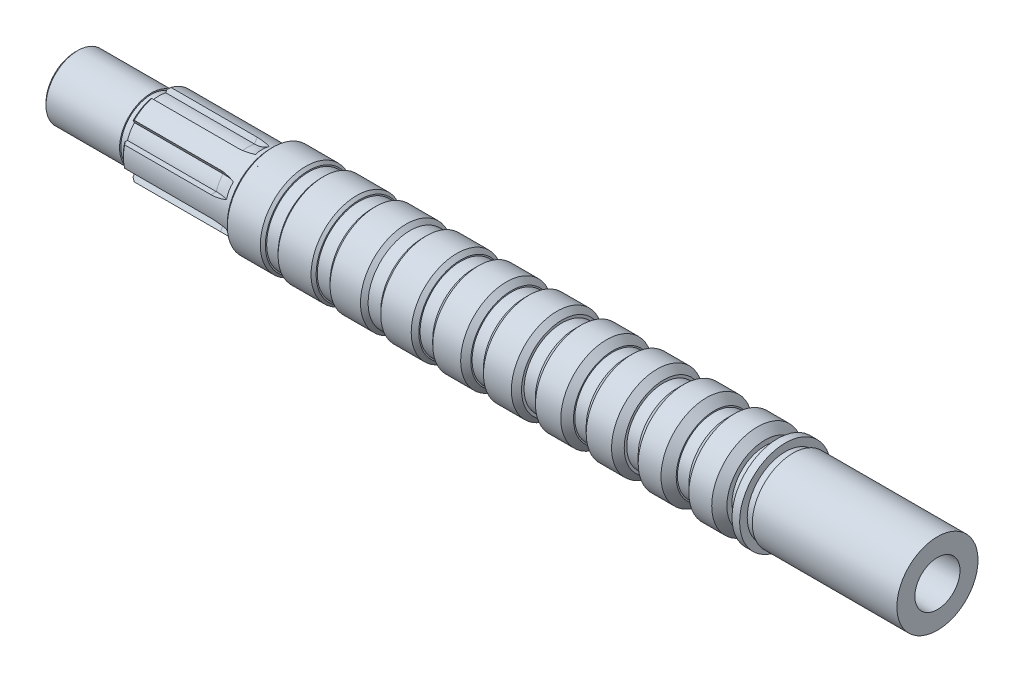
SolidWorks part; units mm, degrees
ref_plane "前视基准面" through (0, 0, 0) normal (0, 0, 1) x (1, 0, 0)
ref_plane "上视基准面" through (0, 0, 0) normal (0, 1, 0) x (1, 0, 0)
ref_plane "右视基准面" through (0, 0, 0) normal (1, 0, 0) x (0, 0, -1)
sketch "草图1" plane through (0, 0, 0) normal (1, 0, 0) x (0, 0, -1)
  circle A0 centre (0, 0) radius 12.5
  dimension "D1" = 25
extrude "凸台-拉伸1" add sketch "草图1" along normal blind 340
sketch "草图3" plane through (340, 0, 0) normal (1, 0, 0) x (0, 0, -1)
  circle A0 centre (0, 0) radius 16
  dimension "D1" = 32
extrude "凸台-拉伸2" add sketch "草图3" against normal blind 60
sketch "草图4" plane through (280, 0, 0) normal (-1, 0, 0) x (0, 0, 1)
  circle A2 centre (0, 0) radius 15
  circle A3 centre (0, 0) radius 15
  dimension "D1" = 1
extrude "切除-拉伸1" cut sketch "草图4" against normal blind 3 flip side to cut
sketch "草图5" plane through (280, 0, 0) normal (-1, 0, 0) x (0, 0, 1)
  circle A0 centre (0, 0) radius 18
  dimension "D1" = 36
extrude "凸台-拉伸3" add sketch "草图5" along normal blind 3
ref_plane "基准面1" through (272, 0, 0) normal (-1, 0, 0) x (0, 0, 1)
sketch "草图6" plane through (272, 0, 0) normal (-1, 0, 0) x (0, 0, 1)
  circle A0 centre (0, 0) radius 18
  dimension "D1" = 36
extrude "凸台-拉伸4" add sketch "草图6" along normal blind 15
pattern_linear "阵列(线性)1" count 10 spacing 20 along (-1, 0, 0) of "凸台-拉伸4"
sketch "草图7" plane through (92, 0, 0) normal (1, 0, 0) x (0, 0, -1)
  circle A2 centre (0, 0) radius 16.5
  circle A3 centre (0, 0) radius 16.5
  dimension "D1" = 1.5
extrude "凸台-拉伸5" add sketch "草图7" along normal up to next
sketch "草图8" plane through (112, 0, 0) normal (1, 0, 0) x (0, 0, -1)
  circle A2 centre (0, 0) radius 16.5
  circle A3 centre (0, 0) radius 16.5
  dimension "D1" = 1.5
extrude "凸台-拉伸6" add sketch "草图8" along normal up to next
sketch "草图9" plane through (132, 0, 0) normal (1, 0, 0) x (0, 0, -1)
  circle A2 centre (0, 0) radius 16.5
  circle A3 centre (0, 0) radius 16.5
  dimension "D1" = 1.5
extrude "凸台-拉伸7" add sketch "草图9" along normal up to next
sketch "草图10" plane through (152, 0, 0) normal (1, 0, 0) x (0, 0, -1)
  circle A2 centre (0, 0) radius 16
  circle A3 centre (0, 0) radius 16
  dimension "D1" = 2
extrude "凸台-拉伸8" add sketch "草图10" along normal up to next
sketch "草图11" plane through (172, 0, 0) normal (1, 0, 0) x (0, 0, -1)
  circle A2 centre (0, 0) radius 15.5
  circle A3 centre (0, 0) radius 15.5
  dimension "D1" = 2.5
extrude "凸台-拉伸9" add sketch "草图11" along normal up to next
sketch "草图12" plane through (192, 0, 0) normal (1, 0, 0) x (0, 0, -1)
  circle A2 centre (0, 0) radius 15
  circle A3 centre (0, 0) radius 15
  dimension "D1" = 3
extrude "凸台-拉伸10" add sketch "草图12" along normal up to next
sketch "草图13" plane through (212, 0, 0) normal (1, 0, 0) x (0, 0, -1)
  circle A2 centre (0, 0) radius 15
  circle A3 centre (0, 0) radius 15
  dimension "D1" = 3
extrude "凸台-拉伸11" add sketch "草图13" along normal up to next
sketch "草图14" plane through (232, 0, 0) normal (1, 0, 0) x (0, 0, -1)
  circle A2 centre (0, 0) radius 14.5
  circle A3 centre (0, 0) radius 14.5
  dimension "D1" = 3.5
extrude "凸台-拉伸12" add sketch "草图14" along normal up to next
sketch "草图15" plane through (252, 0, 0) normal (1, 0, 0) x (0, 0, -1)
  circle A2 centre (0, 0) radius 14.5
  circle A3 centre (0, 0) radius 14.5
  dimension "D1" = 3.5
extrude "凸台-拉伸13" add sketch "草图15" along normal up to next
sketch "草图16" plane through (272, 0, 0) normal (1, 0, 0) x (0, 0, -1)
  circle A2 centre (0, 0) radius 13
  circle A3 centre (0, 0) radius 13
  dimension "D1" = 5
extrude "凸台-拉伸14" add sketch "草图16" along normal up to next
sketch "草图17" plane through (77, 0, 0) normal (-1, 0, 0) x (0, 0, 1)
  circle A0 centre (0, 0) radius 15
  dimension "D1" = 30
extrude "凸台-拉伸15" add sketch "草图17" along normal blind 44
sketch "草图18" plane through (33, 0, 0) normal (-1, 0, 0) x (0, 0, 1)
  circle A0 centre (0, 0) radius 12.5
  circle A1 centre (0, 0) radius 12
  dimension "D1" = 25
  dimension "D2" = 0.5
extrude "切除-拉伸2" cut sketch "草图18" along normal blind 3
chamfer "倒角6" distance 1 angle 45 1 edges at (0, 0, -12.5)
sketch "草图20" plane through (0, 0, 0) normal (0, 0, 1) x (1, 0, 0)
  line L0 (33, 13) -> (68, 13)
  line L1 (33, 15) -> (33, -15) construction
  line L2 (19.8, 0) -> (-19.8, 0) construction
  arc A0 (68, 13) -> (75.9564, 17.7934) centre (68, 22) ccw
  dimension "D1" = 9
  dimension "D2" = 13
  dimension "D3" = 35
sketch "草图21" plane through (33, 0, 0) normal (-1, 0, 0) x (0, 0, 1)
  line L0 (14.4568, 4) -> (12.3693, 4) construction
  line L1 (12.3693, -4) -> (14.4568, -4) construction
  line L5 (2.7206, -12.7121) -> (3.7643, -14.52) construction
  line L6 (10.6925, -10.52) -> (9.6488, -8.7121) construction
  line L7 (-9.6488, -8.7121) -> (-10.6925, -10.52) construction
  line L8 (-3.7643, -14.52) -> (-2.7206, -12.7121) construction
  line L9 (-12.3693, 4) -> (-14.4568, 4) construction
  line L10 (-14.4568, -4) -> (-12.3693, -4) construction
  line L11 (-2.7206, 12.7121) -> (-3.7643, 14.52)
  line L12 (-10.6925, 10.52) -> (-9.6488, 8.7121) construction
  line L13 (9.6488, 8.7121) -> (10.6925, 10.52) construction
  line L14 (3.7643, 14.52) -> (2.7206, 12.7121)
  arc A1 (-3.7643, -14.52) -> (3.7643, -14.52) centre (0, 0) ccw construction
  arc A2 (12.3693, 4) -> (9.6488, 8.7121) centre (0, 0) ccw construction
  circle A3 centre (0, 0) radius 13 construction
  arc A4 (-3.7643, 14.52) -> (-10.6925, 10.52) centre (0, 0) ccw construction
  arc A5 (-2.7206, 12.7121) -> (-9.6488, 8.7121) centre (0, 0) ccw construction
  arc A6 (-9.6488, 8.7121) -> (-12.3693, 4) centre (0, 0) ccw construction
  arc A7 (-10.6925, 10.52) -> (-14.4568, 4) centre (0, 0) ccw construction
  arc A8 (-14.4568, 4) -> (-14.4568, -4) centre (0, 0) ccw construction
  arc A9 (-12.3693, 4) -> (-12.3693, -4) centre (0, 0) ccw construction
  arc A10 (-14.4568, -4) -> (-10.6925, -10.52) centre (0, 0) ccw construction
  arc A11 (-12.3693, -4) -> (-9.6488, -8.7121) centre (0, 0) ccw construction
  arc A12 (-10.6925, -10.52) -> (-3.7643, -14.52) centre (0, 0) ccw construction
  arc A13 (-9.6488, -8.7121) -> (-2.7206, -12.7121) centre (0, 0) ccw construction
  arc A14 (-2.7206, -12.7121) -> (2.7206, -12.7121) centre (0, 0) ccw construction
  arc A15 (2.7206, -12.7121) -> (9.6488, -8.7121) centre (0, 0) ccw construction
  arc A16 (3.7643, -14.52) -> (10.6925, -10.52) centre (0, 0) ccw construction
  arc A17 (14.4568, 4) -> (10.6925, 10.52) centre (0, 0) ccw construction
  arc A18 (10.6925, -10.52) -> (14.4568, -4) centre (0, 0) ccw construction
  arc A19 (9.6488, -8.7121) -> (12.3693, -4) centre (0, 0) ccw construction
  arc A20 (12.3693, -4) -> (12.3693, 4) centre (0, 0) ccw construction
  arc A21 (14.4568, -4) -> (14.4568, 4) centre (0, 0) ccw construction
  arc A22 (9.6488, 8.7121) -> (2.7206, 12.7121) centre (0, 0) ccw construction
  arc A23 (2.7206, 12.7121) -> (-2.7206, 12.7121) centre (0, 0) ccw
  arc A24 (10.6925, 10.52) -> (3.7643, 14.52) centre (0, 0) ccw construction
  arc A25 (3.7643, 14.52) -> (-3.7643, 14.52) centre (0, 0) ccw
  dimension "D1" = 26
  dimension "D2" = 8
  dimension "D3" = 6
sweep "切除-扫描1" cut profiles "草图21" path "草图20"
pattern_circular "阵列(圆周)1" count 6 over 360 about axis through (33, 0, 0) along (1, 0, 0) of "切除-扫描1"
sketch "草图22" plane through (0, 0, 0) normal (-1, 0, 0) x (0, 0, 1)
  circle A0 centre (0, 0) radius 6
  dimension "D1" = 12
extrude "切除-拉伸3" cut sketch "草图22" against normal through all
chamfer "倒角1" distance 1 angle 45 4 edges at (112, 0, 18) (97, 0, 18) (92, 0, 18) (77, 0, 18)
chamfer "倒角2" distance 1.5 angle 45 4 edges at (132, 0, 18) (117, 0, 18) (152, 0, 18) (137, 0, 18)
chamfer "倒角3" distance 2 angle 45 4 edges at (192, 0, 18) (177, 0, 18) (172, 0, 18) (157, 0, 18)
chamfer "倒角4" distance 2.5 angle 45 4 edges at (232, 0, 18) (217, 0, 18) (212, 0, 18) (197, 0, 18)
chamfer "倒角5" distance 3 angle 45 4 edges at (272, 0, 18) (257, 0, 18) (252, 0, 18) (237, 0, 18)
sketch "草图25" plane through (0, 0, 0) normal (0, 1, 0) x (1, 0, 0)
  line L0 (340, 0) -> (340, 8.89)
  line L1 (340, -16) -> (340, 16) construction
  line L2 (340, 8.89) -> (280, 7.3915)
  line L3 (280, 7.3915) -> (280, 0)
  line L4 (-19.8, 0) -> (19.8, 0) construction
  line L5 (280, 0) -> (340, 0) construction
  line L6 (340, 8.39) -> (319.98, 8.39) construction
  line L7 (340, 0) -> (280, 0)
  dimension "D1" = 0.5
  dimension "D2" = 20.02
  dimension "D3" = 60
  dimension "D4" = 17.78
revolve "切除-旋转1" cut sketch "草图25" angle 360 about L7
sketch "草图26" plane through (280, 0, 0) normal (1, 0, 0) x (0, 0, -1)
  circle A0 centre (0, 0) radius 8
  dimension "D1" = 16
extrude "切除-拉伸6" cut sketch "草图26" against normal blind 10
chamfer "倒角7" distance 1 angle 45 6 edges at (33, 12.9904, 7.5) (33, 0, 15) (33, -12.9904, 7.5) (33, -12.9904, -7.5) (33, 0, -15) (33, 12.9904, -7.5)
